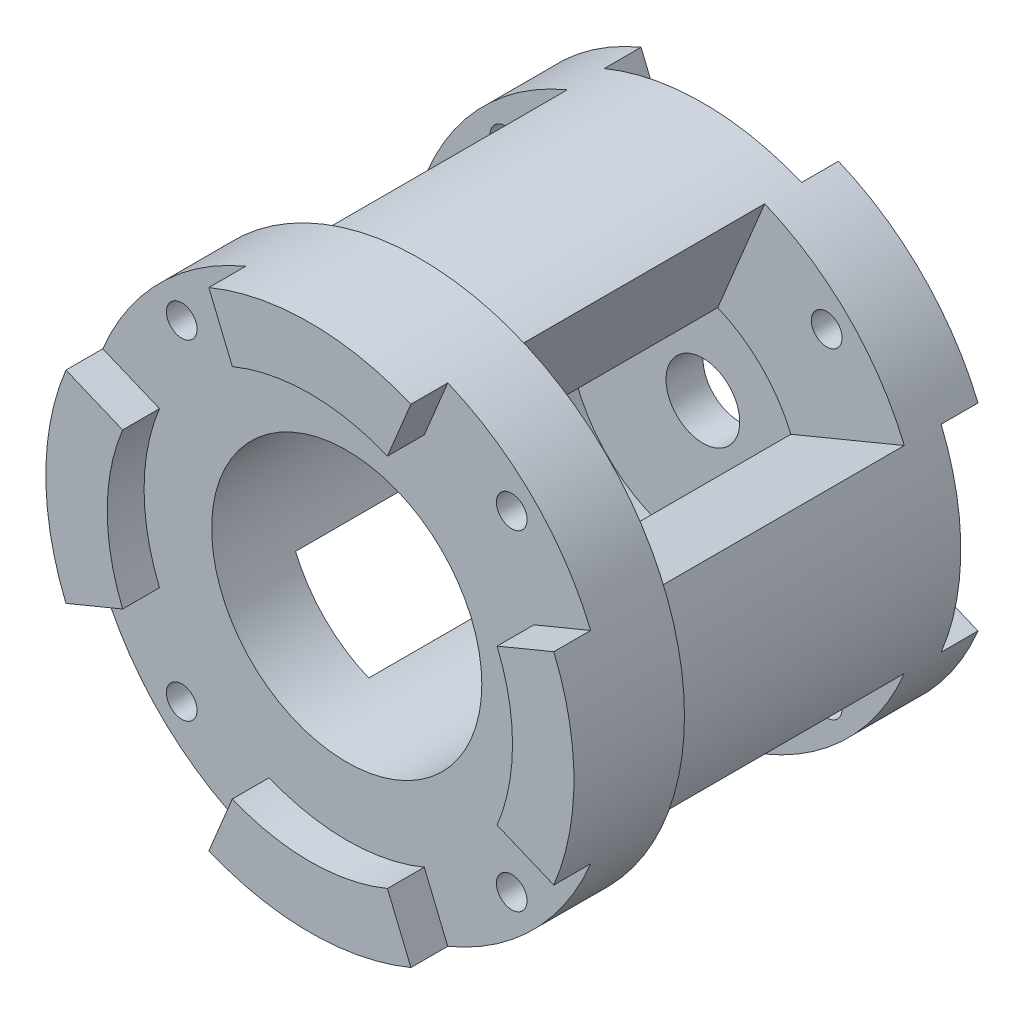
SolidWorks part; units mm, degrees
ref_plane "Front Plane" through (0, 0, 0) normal (0, 0, 1) x (1, 0, 0)
ref_plane "Top Plane" through (0, 0, 0) normal (0, 1, 0) x (1, 0, 0)
ref_plane "Right Plane" through (0, 0, 0) normal (1, 0, 0) x (0, 0, -1)
sketch "Sketch1" plane through (0, 0, 0) normal (0, 0, 1) x (1, 0, 0)
  line L0 (-18.5, 0) -> (-21, 0) construction
  line L1 (-13.0815, 13.0815) -> (13.0815, -13.0815) construction
  line L2 (-13.0815, -13.0815) -> (13.0815, 13.0815) construction
  line L3 (-13.0815, 13.0815) -> (13.0815, 13.0815) construction
  line L4 (0, 0) -> (-8.0364, 19.4015) construction
  line L5 (0, 0) -> (8.0364, 19.4015) construction
  line L6 (0, 0) -> (0, 21) construction
  line L7 (-6.1229, 14.7821) -> (-8.0364, 19.4015)
  line L8 (6.1229, 14.7821) -> (8.0364, 19.4015)
  line L9 (-14.7821, -6.1229) -> (-19.4015, -8.0364)
  line L10 (-14.7821, 6.1229) -> (-19.4015, 8.0364)
  line L11 (-6.1229, -14.7821) -> (-8.0364, -19.4015)
  line L12 (6.1229, -14.7821) -> (8.0364, -19.4015)
  line L13 (14.7821, 6.1229) -> (19.4015, 8.0364)
  line L14 (14.7821, -6.1229) -> (19.4015, -8.0364)
  line L15 (0, 16) -> (0, 11)
  circle A0 centre (0, 0) radius 21
  circle A1 centre (0, 0) radius 18.5 construction
  circle A2 centre (-13.0815, 13.0815) radius 1.25
  circle A3 centre (13.0815, 13.0815) radius 1.25
  circle A4 centre (13.0815, -13.0815) radius 1.25
  circle A5 centre (-13.0815, -13.0815) radius 1.25
  arc A6 (-6.1229, 14.7821) -> (6.1229, 14.7821) centre (0, 0) cw
  arc A7 (-14.7821, 6.1229) -> (-14.7821, -6.1229) centre (0, 0) ccw
  arc A8 (6.1229, -14.7821) -> (-6.1229, -14.7821) centre (0, 0) cw
  arc A9 (14.7821, -6.1229) -> (14.7821, 6.1229) centre (0, 0) ccw
  circle A10 centre (0, 0) radius 11
  circle A11 centre (0, 0) radius 3
  point P16 (0, 13.0815)
  point P20 (0, 16)
  dimension "D1" = 42
  dimension "D3" = 2.5
  dimension "D7" = 6
  dimension "D2" = 2.5
  dimension "D4" = 5
  dimension "D5" = 45
  dimension "D6" = 5
extrude "Boss-Extrude1" add sketch "Sketch1" along normal blind 3 contours L14 A9 L13 A0 L8 A6 L7 L10 A7 L9 L11 A8 L12 A5 A4 A3 A2 | A7 L10 A0 L9 | L7 A6 L8 A0 | A9 L14 A0 L13 | L12 A8 L11 A0 region at (-3.0144, 15.1544, 0) region at (0, 18.1379, 0) region at (-18.1379, 0, 0) region at (18.1379, 0, 0) region at (0, -18.1379, 0)
extrude "Boss-Extrude2" add sketch "Sketch1<3>" against normal blind 3 contours L14 A9 L13 A0 L8 A6 L7 L10 A7 L9 L11 A8 L12 A5 A4 A3 A2 | A10 A11 region at (7.5582, 7.5582, 0) region at (-3.0144, 15.1544, 0)
sketch "Sketch1<3>" plane through (0, 0, 0) normal (0, 0, 1) x (1, 0, 0) same geometry as "Sketch1"
sketch "Sketch2" plane through (0, 0, 3) normal (0, 0, 1) x (1, 0, 0)
  line L0 (-19.4015, 8.0364) -> (-10.1627, 4.2095)
  line L1 (-19.4015, -8.0364) -> (-10.1627, -4.2095)
  line L2 (-14.7821, 6.1229) -> (-19.4015, 8.0364) construction
  line L3 (-14.7821, -6.1229) -> (-19.4015, -8.0364) construction
  line L4 (-13.0815, -13.0815) -> (13.0815, 13.0815) construction
  line L5 (8.0364, 19.4015) -> (4.2095, 10.1627)
  line L6 (-8.0364, 19.4015) -> (-4.2095, 10.1627)
  line L7 (19.4015, -8.0364) -> (10.1627, -4.2095)
  line L8 (19.4015, 8.0364) -> (10.1627, 4.2095)
  line L9 (-8.0364, -19.4015) -> (-4.2095, -10.1627)
  line L10 (8.0364, -19.4015) -> (4.2095, -10.1627)
  circle A0 centre (0, 0) radius 11 construction
  arc A1 (-19.4015, 8.0364) -> (-19.4015, -8.0364) centre (0, 0) ccw
  arc A2 (-10.1627, 4.2095) -> (-10.1627, -4.2095) centre (0, 0) ccw
  arc A3 (8.0364, 19.4015) -> (-8.0364, 19.4015) centre (0, 0) ccw
  arc A4 (4.2095, 10.1627) -> (-4.2095, 10.1627) centre (0, 0) ccw
  arc A5 (19.4015, -8.0364) -> (19.4015, 8.0364) centre (0, 0) ccw
  arc A6 (10.1627, -4.2095) -> (10.1627, 4.2095) centre (0, 0) ccw
  arc A7 (-8.0364, -19.4015) -> (8.0364, -19.4015) centre (0, 0) ccw
  arc A8 (-4.2095, -10.1627) -> (4.2095, -10.1627) centre (0, 0) ccw
  circle M17 centre (0, 0) radius 21
  circle M18 centre (0, 0) radius 11
  dimension "D1" = 4
extrude "Boss-Extrude3" add sketch "Sketch2" along normal blind 20 contours L6 L5 M17 M18 | L1 L0 M17 M18 | L10 L9 M17 M18 | L8 L7 M17 M18 region at (-16.0995, 0, 3) region at (0, 16.0995, 3) region at (0, -16.0995, 3) region at (16.0995, 0, 3)
ref_plane "Plane2" through (0, 0, 23) normal (0, 0, 1) x (1, 0, 0)
sketch "Sketch5" plane through (0, 0, 23) normal (0, 0, 1) x (1, 0, 0)
  line L0 (-16.5, 0) -> (-21.5, 0) construction
  line L1 (0, 0) -> (-15.2028, 15.2028) construction
  line L2 (-15.2028, 15.2028) -> (-13.435, 13.435) construction
  circle A0 centre (0, 0) radius 21 construction
  circle A1 centre (0, 0) radius 21 construction
  circle A2 centre (0, 0) radius 11 construction
  circle A3 centre (0, 0) radius 11
  circle A7 centre (-13.0815, 13.0815) radius 1.25 construction
  circle A11 centre (-13.0815, 13.0815) radius 1.25 construction
  circle A12 centre (0, 0) radius 16.5 construction
  circle A13 centre (0, 0) radius 21.5
  circle A14 centre (-13.435, 13.435) radius 1.25
  circle A15 centre (13.435, 13.435) radius 1.25
  circle A16 centre (13.435, -13.435) radius 1.25
  circle A17 centre (-13.435, -13.435) radius 1.25
  circle A18 centre (0, 0) radius 19 construction
  dimension "D1" = 33
  dimension "D4" = 2.5
  dimension "D2" = 5
  dimension "D3" = 2.5
  dimension "D5" = 4
extrude "Boss-Extrude4" add sketch "Sketch5" along normal blind 6
sketch "Sketch6" plane through (0, 0, 29) normal (0, 0, 1) x (1, 0, 0)
  line L0 (-14.7821, 6.1229) -> (-19.4015, 8.0364) construction
  line L1 (-16.5, 0) -> (-21.5, 0) construction
  line L2 (-14.7821, -6.1229) -> (-19.4015, -8.0364) construction
  line L3 (-15.244, 6.3143) -> (-19.8634, 8.2277)
  line L4 (-6.1229, 14.7821) -> (-8.0364, 19.4015) construction
  line L5 (-15.244, -6.3143) -> (-19.8634, -8.2277)
  line L6 (-8.2277, 19.8634) -> (-6.3143, 15.244)
  line L7 (8.2277, 19.8634) -> (6.3143, 15.244)
  line L8 (19.8634, 8.2277) -> (15.244, 6.3143)
  line L9 (15.244, -6.3143) -> (19.8634, -8.2277)
  line L10 (6.1229, 14.7821) -> (8.0364, 19.4015) construction
  line L11 (6.3143, -15.244) -> (8.2277, -19.8634)
  line L12 (-8.2277, -19.8634) -> (-6.3143, -15.244)
  line L14 (14.7821, 6.1229) -> (19.4015, 8.0364) construction
  line L24 (14.7821, -6.1229) -> (19.4015, -8.0364) construction
  line L36 (6.1229, -14.7821) -> (8.0364, -19.4015) construction
  line L50 (-6.1229, -14.7821) -> (-8.0364, -19.4015) construction
  line L58 (-6.1229, 14.7821) -> (-8.0364, 19.4015) construction
  line L59 (6.1229, 14.7821) -> (8.0364, 19.4015) construction
  line L60 (14.7821, 6.1229) -> (19.4015, 8.0364) construction
  line L61 (14.7821, -6.1229) -> (19.4015, -8.0364) construction
  line L62 (6.1229, -14.7821) -> (8.0364, -19.4015) construction
  line L63 (-6.1229, -14.7821) -> (-8.0364, -19.4015) construction
  line L64 (-14.7821, -6.1229) -> (-19.4015, -8.0364) construction
  line L65 (-14.7821, 6.1229) -> (-19.4015, 8.0364) construction
  arc A0 (-14.7821, 6.1229) -> (-14.7821, -6.1229) centre (0, 0) ccw construction
  circle A1 centre (0, 0) radius 21.5 construction
  circle A2 centre (0, 0) radius 21.5
  arc A3 (6.1229, 14.7821) -> (-6.1229, 14.7821) centre (0, 0) ccw construction
  circle A4 centre (0, 0) radius 16.5
  arc A9 (14.7821, -6.1229) -> (14.7821, 6.1229) centre (0, 0) ccw construction
  circle A15 centre (0, 0) radius 21 construction
  arc A23 (-6.1229, -14.7821) -> (6.1229, -14.7821) centre (0, 0) ccw construction
  arc A33 (6.1229, 14.7821) -> (-6.1229, 14.7821) centre (0, 0) ccw construction
  arc A34 (14.7821, -6.1229) -> (14.7821, 6.1229) centre (0, 0) ccw construction
  arc A35 (-6.1229, -14.7821) -> (6.1229, -14.7821) centre (0, 0) ccw construction
  arc A36 (-14.7821, 6.1229) -> (-14.7821, -6.1229) centre (0, 0) ccw construction
  circle A37 centre (0, 0) radius 21 construction
  circle M47 centre (0, 0) radius 21.5
  dimension "D1" = 5
extrude "Boss-Extrude5" add sketch "Sketch6" along normal blind 3 contours A36 L65 L64 | A33 L59 L58 | A34 L61 L60 | A35 L63 L62 | A4 L7 L6 M47 | A4 L9 L8 M47 | A4 L12 L11 M47 | A4 L3 L5 M47 region at (-18.6223, 0, 29) region at (0, 18.6223, 29) region at (0, -18.6223, 29) region at (18.6223, 0, 29)
